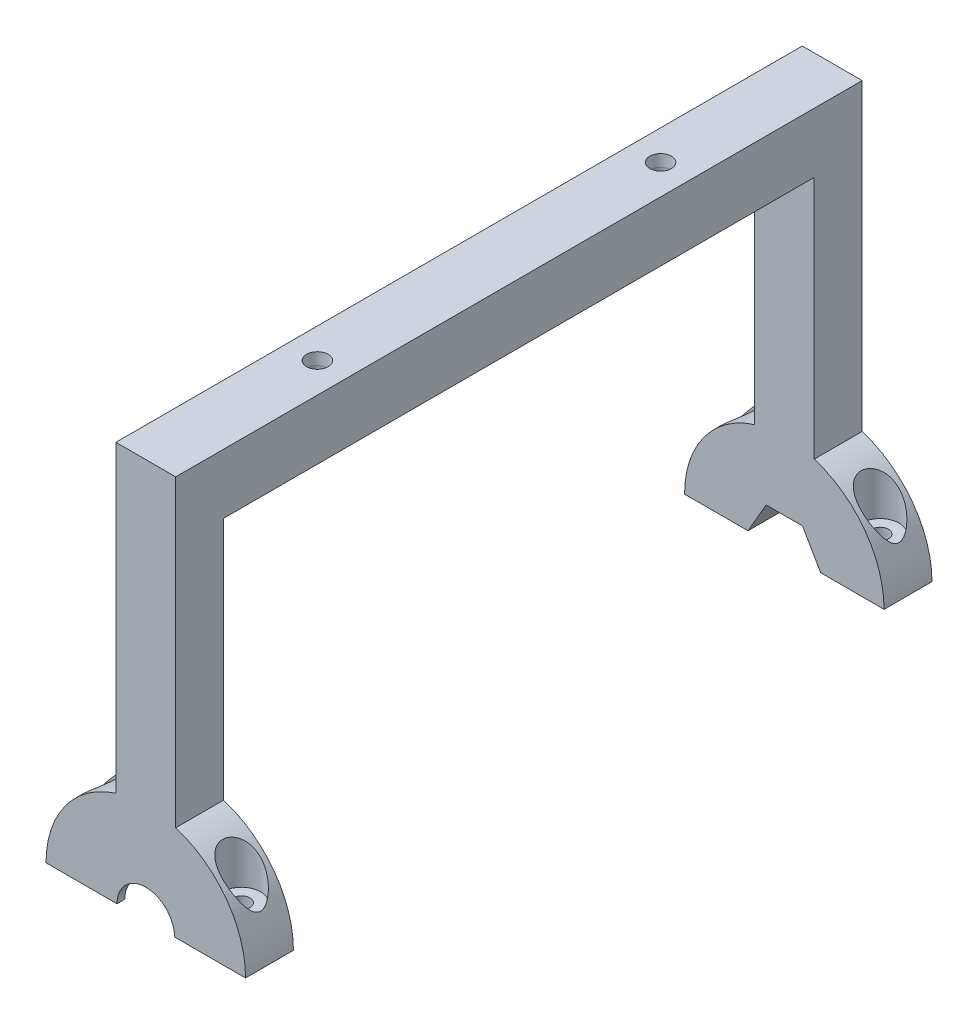
SolidWorks part; units mm, degrees
ref_plane "Front Plane" through (0, 0, 0) normal (0, 0, 1) x (1, 0, 0)
ref_plane "Top Plane" through (0, 0, 0) normal (0, 1, 0) x (1, 0, 0)
ref_plane "Right Plane" through (0, 0, 0) normal (1, 0, 0) x (0, 0, -1)
sketch "Sketch2" plane through (0, 0, 0) normal (0, 0, 1) x (1, 0, 0)
  line L1 (-7.5, 7.5) -> (7.5, 7.5)
  line L2 (-7.5, 7.5) -> (-7.5, -7.5)
  line L3 (-7.5, -7.5) -> (7.5, -7.5)
  line L4 (7.5, 7.5) -> (7.5, -7.5)
  line L5 (-7.5, 7.5) -> (7.5, -7.5) construction
  line L6 (-7.5, -7.5) -> (7.5, 7.5) construction
  point P0 (0, 0)
  dimension "D1" = 15
extrude "Boss-Extrude1" add sketch "Sketch2" along normal blind 86
sketch "Sketch3" plane through (0, -7.5, 0) normal (0, -1, 0) x (1, 0, 0)
  line L0 (-7.5, 86) -> (-7.5, 0) construction
  line L1 (7.5, 86) -> (-7.5, 86)
  line L2 (7.5, 86) -> (7.5, 74)
  line L3 (7.5, 74) -> (-7.5, 74)
  line L4 (-7.5, 86) -> (-7.5, 74)
  dimension "D1" = 12
extrude "Boss-Extrude2" add sketch "Sketch3" along normal blind 85
sketch "Sketch4" plane through (0, 0, 86) normal (0, 0, 1) x (1, 0, 0)
  line L0 (7.5, -92.5) -> (-7.5, -92.5) construction
  line L1 (-25, -92.5) -> (25, -92.5)
  arc A0 (25, -92.5) -> (-25, -92.5) centre (0, -92.5) ccw
  dimension "D1" = 50
extrude "Boss-Extrude3" add sketch "Sketch4" against normal up to surface (12 mm away) up to face at (0, -50, 74)
ref_plane "Plane1" through (0, -72.66, 0) normal (0, -1, 0) x (-1, 0, 0)
sketch "Sketch6" plane through (0, -72.66, 0) normal (0, -1, 0) x (-1, 0, 0)
  line L0 (-25, -74) -> (-25, -86) construction
  line L1 (-25, -86) -> (-7.5, -86) construction
  circle A0 centre (-18, -80) radius 4.75
  circle A1 centre (18, -80) radius 4.75
  circle A2 centre (18, -80) radius 2.1
  circle A3 centre (-18, -80) radius 2.1
  dimension "D2" = 9.5
  dimension "D3" = 9.5
  dimension "D4" = 4.2
  dimension "D5" = 4.2
  dimension "D1" = 7
  dimension "D6" = 6
  dimension "D7" = 36
extrude "Cut-Extrude1" cut sketch "Sketch6" along normal blind 10 and the other way up to next
extrude "Cut-Extrude2" cut sketch "Sketch6<2>" along normal up to next contours A3 | A2 region at (18, -72.66, 80)
sketch "Sketch6<2>" plane through (0, -72.66, 0) normal (0, -1, 0) x (-1, 0, 0) same geometry as "Sketch6"
sketch "Sketch7" plane through (0, 7.5, 0) normal (0, 1, 0) x (1, 0, 0)
  line L0 (0, -86) -> (0, 0) construction
  line L1 (7.5, -86) -> (-7.5, -86) construction
  circle A0 centre (0, -43) radius 2.45
  dimension "D1" = 4.9
hole_wizard "CSK for M3 Oval Head Machine Screw1" positions "Sketch11" profile "Sketch12" countersink size "M3" standard "ANSI Metric" end condition through all
sketch "Sketch11" plane through (0, 7.5, 0) normal (0, 1, 0) x (1, 0, 0)
  point P0 (0, -43)
sketch "Sketch12" plane through (0, 7.5, 43) normal (1, 0, 0) x (0, 0, 1)
  line L0 (0, 0) -> (0, 100)
  line L1 (0, 100) -> (2.5, 100)
  line L2 (2.5, 100) -> (2.5, 2.8601)
  line L3 (2.5, 2.8601) -> (2.7, 0)
  line L5 (2.7, 0) -> (0, 0)
  line L6 (-2.5, 2.8601) -> (-2.7, 0) construction
  line L11 (0, -6.35) -> (0, 107.95) construction
  dimension "Thru Hole Dia." = 5
  dimension "Thru Hole Depth" = 100
  dimension "Near C'Sink Dia." = 5.4
  dimension "Near C'Sink Angle" = 8
mirror "Mirror1" about plane through (0, 0, 0) normal (0, 0, 1) of bodies 113 106
sketch "Sketch8" plane through (0, 0, 86) normal (0, 0, 1) x (1, 0, 0)
  line L0 (25, -92.5) -> (-25, -92.5) construction
  circle A0 centre (0, -92.5) radius 7.2
  dimension "D1" = 14.4
extrude "Cut-Extrude4" cut sketch "Sketch8" against normal up to next
sketch "Sketch9" plane through (0, 0, 86) normal (0, 0, 1) x (1, 0, 0)
  circle A0 centre (0, -92.5) radius 13.1
  dimension "D1" = 26.2
extrude "Cut-Extrude5" cut sketch "Sketch9" against normal blind 8.15 from offset 1.925 offset against normal yes
sketch "Sketch10" plane through (0, 0, -86) normal (0, 0, -1) x (-1, 0, 0)
  line L0 (-25, -92.5) -> (25, -92.5) construction
  line L1 (9.1, -92.5) -> (4.55, -84.6192)
  line L2 (4.55, -84.6192) -> (-4.55, -84.6192)
  line L3 (-4.55, -84.6192) -> (-9.1, -92.5)
  line L4 (-9.1, -92.5) -> (-4.55, -100.3808)
  line L5 (-4.55, -100.3808) -> (4.55, -100.3808)
  line L6 (4.55, -100.3808) -> (9.1, -92.5)
  circle A0 centre (0, -92.5) radius 7.8808 construction
  dimension "D1" = 18.2
extrude "Cut-Extrude6" cut sketch "Sketch10" against normal up to next
